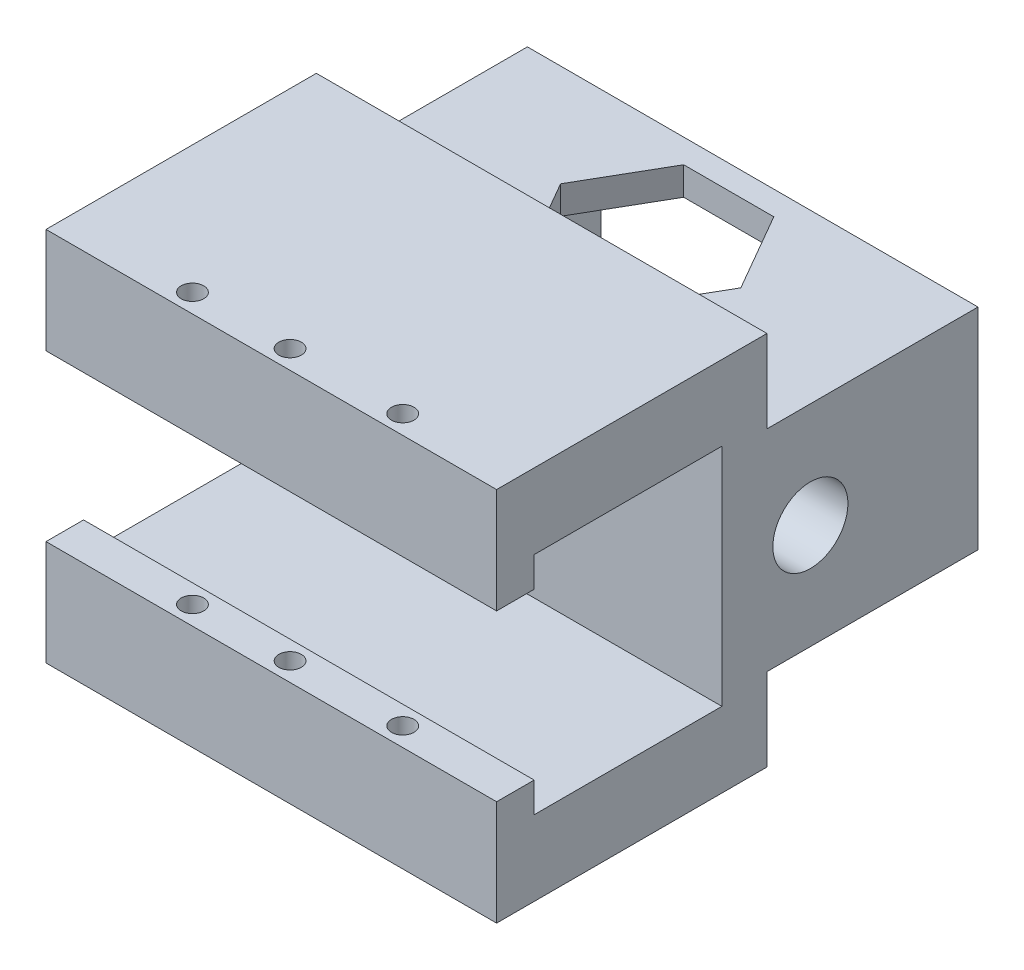
SolidWorks part; units mm, degrees
ref_plane "前视基准面" through (0, 0, 0) normal (0, 0, 1) x (1, 0, 0)
ref_plane "上视基准面" through (0, 0, 0) normal (0, 1, 0) x (1, 0, 0)
ref_plane "右视基准面" through (0, 0, 0) normal (1, 0, 0) x (0, 0, -1)
sketch "草图1" plane through (0, 0, 0) normal (0, 0, 1) x (1, 0, 0)
  line L1 (30, -25) -> (-30, -25)
  line L2 (30, -25) -> (30, 25)
  line L3 (30, 25) -> (-30, 25)
  line L4 (-30, -25) -> (-30, 25)
  line L5 (30, -25) -> (-30, 25) construction
  line L6 (30, 25) -> (-30, -25) construction
  point P0 (0, 0)
  dimension "D1" = 50
  dimension "D2" = 60
extrude "凸台-拉伸1" add sketch "草图1" along normal blind 6
sketch "草图2" plane through (0, 0, 6) normal (0, 0, 1) x (1, 0, 0)
  line L0 (30, -25) -> (30, 25) construction
  line L1 (-30, 25) -> (30, 25)
  line L2 (-30, 25) -> (-30, 15)
  line L3 (-30, 15) -> (30, 15)
  line L4 (30, 25) -> (30, 15)
  line L6 (-30, -25) -> (30, -25)
  line L7 (-30, -25) -> (-30, -15)
  line L8 (-30, -15) -> (30, -15)
  line L9 (30, -25) -> (30, -15)
  dimension "D1" = 10
  dimension "D2" = 10
extrude "凸台-拉伸3" add sketch "草图2" along normal blind 30
sketch "草图3" plane through (0, -15, 0) normal (0, 1, 0) x (1, 0, 0)
  line L0 (30, -36) -> (30, -6) construction
  line L1 (-30, -36) -> (30, -36)
  line L2 (-30, -36) -> (-30, -31)
  line L3 (-30, -31) -> (30, -31)
  line L4 (30, -36) -> (30, -31)
  dimension "D1" = 5
extrude "凸台-拉伸4" add sketch "草图3" along normal blind 4
sketch "草图4" plane through (0, 15, 0) normal (0, -1, 0) x (1, 0, 0)
  line L0 (30, 36) -> (30, 6) construction
  line L1 (-30, 36) -> (30, 36)
  line L2 (-30, 36) -> (-30, 31)
  line L3 (-30, 31) -> (30, 31)
  line L4 (30, 36) -> (30, 31)
  dimension "D1" = 5
extrude "凸台-拉伸5" add sketch "草图4" along normal blind 4
sketch "草图9" plane through (0, 0, 0) normal (0, 0, -1) x (-1, 0, 0)
  line L1 (20.2, -10.25) -> (-20.2, -10.25)
  line L2 (20.2, -10.25) -> (20.2, 10.25)
  line L3 (20.2, 10.25) -> (-20.2, 10.25)
  line L4 (-20.2, -10.25) -> (-20.2, 10.25)
  line L5 (20.2, -10.25) -> (-20.2, 10.25) construction
  line L6 (20.2, 10.25) -> (-20.2, -10.25) construction
  line L7 (30, -14) -> (-30, -14)
  line L8 (30, -14) -> (30, 14)
  line L9 (30, 14) -> (-30, 14)
  line L10 (-30, -14) -> (-30, 14)
  line L11 (30, -14) -> (-30, 14) construction
  line L12 (30, 14) -> (-30, -14) construction
  point P0 (0, 0)
  point P5 (0, 0)
  dimension "D1" = 20.5
  dimension "D2" = 40.4
  dimension "D3" = 28
  dimension "D4" = 60
extrude "凸台-拉伸6" add sketch "草图9" along normal blind 28.1
sketch "草图11" plane through (30, 0, 0) normal (1, 0, 0) x (0, 0, -1)
  circle A0 centre (5.7817, 0) radius 5
  dimension "D1" = 10
extrude "切除-拉伸3" cut sketch "草图11" against normal blind 10
sketch "草图12" plane through (0, 0, -28.1) normal (0, 0, -1) x (-1, 0, 0)
  circle A0 centre (24.8, -5) radius 2.25
  circle A1 centre (24.8, 5) radius 2.25
  circle A2 centre (-24.8, -5) radius 2.25
  circle A3 centre (-24.8, 5) radius 2.25
extrude "切除-拉伸4" cut sketch "草图12" against normal blind 16
sketch "草图13" plane through (0, 14, 0) normal (0, 1, 0) x (1, 0, 0)
  line L1 (-12, 14.5188) -> (-6, 4.1265)
  line L2 (-6, 4.1265) -> (6, 4.1265)
  line L3 (6, 4.1265) -> (12, 14.5188)
  line L4 (12, 14.5188) -> (6, 24.9111)
  line L5 (6, 24.9111) -> (-6, 24.9111)
  line L6 (-6, 24.9111) -> (-12, 14.5188)
  circle A0 centre (0, 14.5188) radius 10.3923 construction
  dimension "D1" = 12
extrude "切除-拉伸5" cut sketch "草图13" against normal through all
sketch "草图15" plane through (0, -11, 0) normal (0, 1, 0) x (1, 0, 0)
  circle A0 centre (15, -33.5) radius 1.5
  circle A1 centre (0, -33.5) radius 1.5
  circle A2 centre (-13, -33.5) radius 1.5
sketch "草图16" plane through (0, 11, 0) normal (0, -1, 0) x (1, 0, 0)
  circle A0 centre (-13, 33.5) radius 1.5
  circle A1 centre (0, 33.5) radius 1.5
  circle A2 centre (15, 33.5) radius 1.5
extrude "切除-拉伸6" cut sketch "草图15" against normal through all
extrude "切除-拉伸7" cut sketch "草图16" against normal through all
